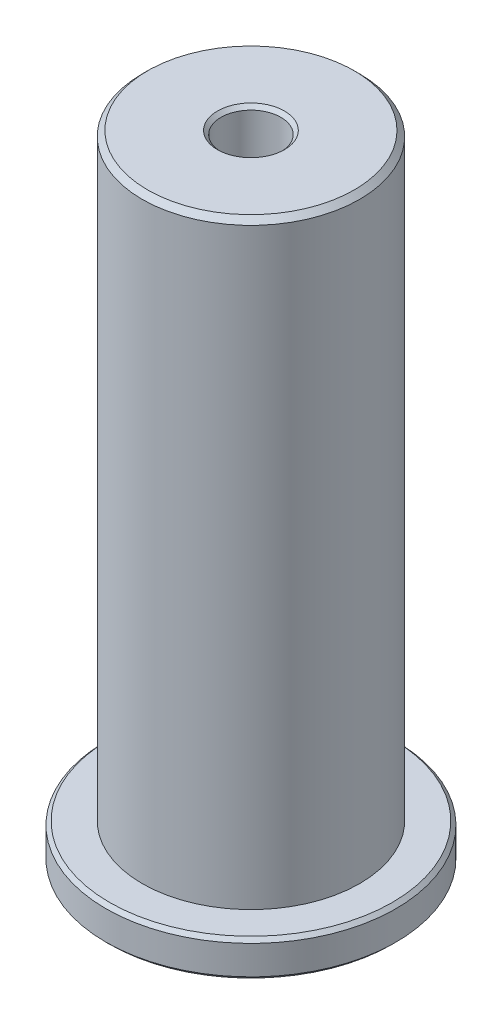
SolidWorks part; units mm, degrees
material "보통 탄소강"
ref_plane "정면" through (0, 0, 0) normal (0, 0, 1) x (1, 0, 0)
ref_plane "윗면" through (0, 0, 0) normal (0, 1, 0) x (1, 0, 0)
ref_plane "우측면" through (0, 0, 0) normal (1, 0, 0) x (0, 0, -1)
sketch "스케치1" plane through (0, 0, 0) normal (0, 1, 0) x (1, 0, 0)
  circle A0 centre (0, 0) radius 8
  circle A1 centre (0, 0) radius 6
  circle A2 centre (0, 0) radius 1.65
  dimension "D1" = 16
  dimension "D2" = 12
  dimension "D3" = 3.3
extrude "보스-돌출1" add sketch "스케치1" along normal blind 2 contours A0 A1 region at (-7.7737, 0, 0)
extrude "보스-돌출2" add sketch "스케치1<3>" along normal blind 35 contours A1 A2 | A2 region at (-5.8303, 0, 0) region at (0, 0, 0)
sketch "스케치1<3>" plane through (0, 0, 0) normal (0, 1, 0) x (1, 0, 0) same geometry as "스케치1"
sketch "스케치2" plane through (0, 0, 0) normal (0, -1, 0) x (1, 0, 0)
  line L1 (-1, 4) -> (1, 4)
  line L2 (-1, 4) -> (-1, -4)
  line L3 (-1, -4) -> (1, -4)
  line L4 (1, 4) -> (1, -4)
  line L5 (-1, 4) -> (1, -4) construction
  line L6 (-1, -4) -> (1, 4) construction
  circle A0 centre (0, 3) radius 1
  circle A1 centre (0, -3) radius 1
  point P0 (0, 0)
  dimension "D1" = 2
  dimension "D2" = 8
extrude "컷-돌출1" cut sketch "스케치2" against normal blind 2 contours A0 | A1 L4 A0 L2 | A1 region at (0, 0, 3) region at (0, 0, 0) region at (0, 0, -3)
extrude "컷-돌출2" cut sketch "스케치1<4>" against normal blind 13 from surface contours A2 region at (0, 0, 0) starting at face at (0, 35, 6)
sketch "스케치1<4>" plane through (0, 0, 0) normal (0, 1, 0) x (1, 0, 0) same geometry as "스케치1"
chamfer "모따기1" distance 0.2 angle 45 3 edges at (0, 2, 8) (0, 0, 8) (0, 35, 1.65)
chamfer "모따기2" distance 0.3 angle 45 1 edges at (0, 35, 6)
sketch "스케치3" plane through (0, 0, 0) normal (0, 0, 1) x (1, 0, 0)
  line L0 (0, 0) -> (0, 22)
  line L1 (1.85, 35) -> (-1.85, 35) construction
  line L2 (0, 22) -> (-1.65, 22)
  line L3 (-1.65, 22) -> (0, 21.3165)
  line L6 (0, -0.6864) -> (0, 4.5094) construction
  dimension "D1" = 67.5
  dimension "D2" = 1.65
  dimension "D3" = 13
revolve "컷-회전1" cut sketch "스케치3" angle 360 about L6 region at (-0.55, 21.7722, 0)
